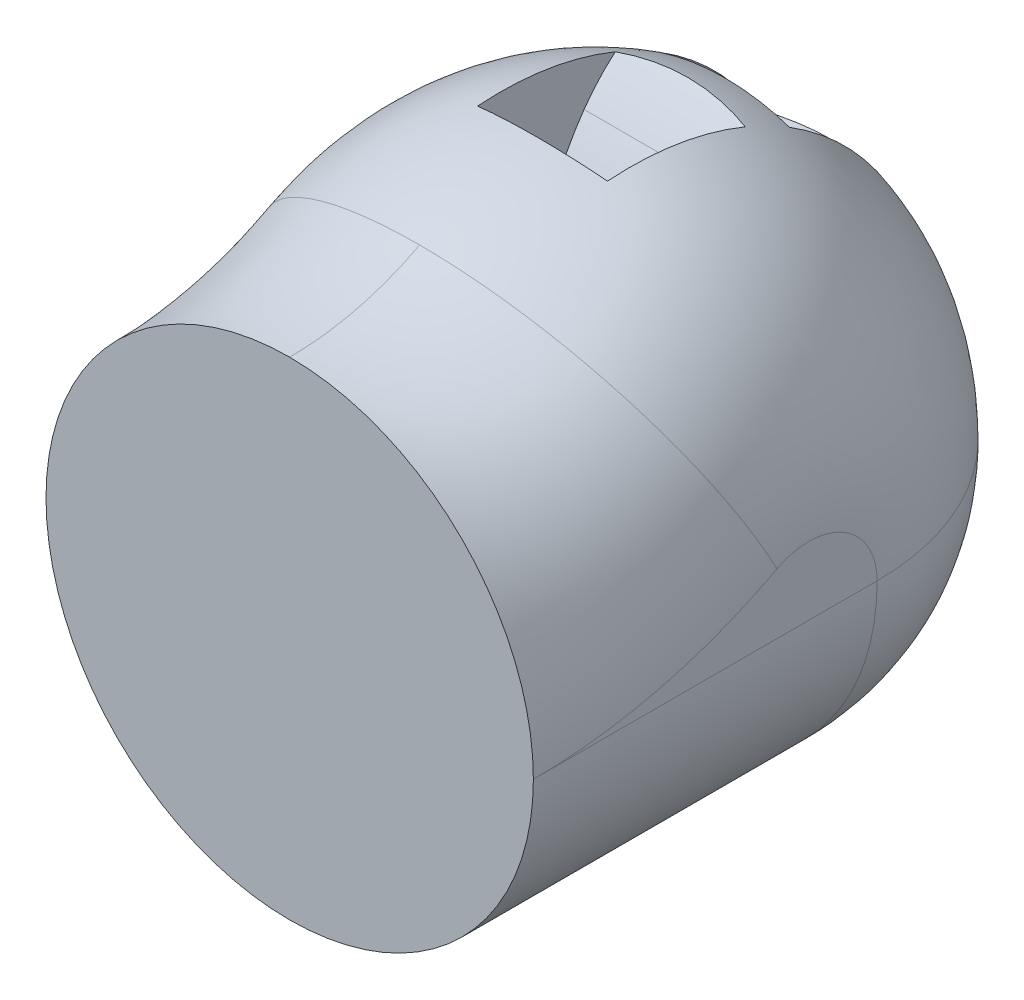
SolidWorks part; units mm, degrees
ref_plane "Front Plane" through (0, 0, 0) normal (0, 0, 1) x (1, 0, 0)
ref_plane "Top Plane" through (0, 0, 0) normal (0, 1, 0) x (1, 0, 0)
ref_plane "Right Plane" through (0, 0, 0) normal (1, 0, 0) x (0, 0, -1)
sketch "Sketch1" plane through (0, 0, 0) normal (1, 0, 0) x (0, 0, -1)
  line L1 (-21.2, 0) -> (-21.2, 18.75)
  line L4 (-21.2, 0) -> (24, 0)
  line L5 (-21.2, 18.75) -> (14.9812, 18.75) construction
  line L7 (-21.2, 0) -> (-21.2, -18.75)
  line L8 (-21.2, -18.75) -> (5.25, -18.75)
  arc A0 (-11.2, 21.2264) -> (24, 0) centre (0, 0) cw
  arc A1 (-21.2, 18.75) -> (-11.2, 21.2264) centre (-21.2, 40.1786) ccw
  arc A2 (24, 0) -> (5.25, -18.75) centre (5.25, 0) cw
  dimension "D2" = 24
  dimension "D1" = 18.75
  dimension "D3" = 10
extrude "Boss-Extrude1" add sketch "Sketch1" along normal blind 18.75 and the other way blind 18.75 contours L5 L1 L4 A0 | A1 L5 A0 | A2 L4 L7 L8 region at (0, 9.0604, -0.1104) region at (0, -8.8681, 0.3992) region at (0, 20.8273, 0.4304)
fillet "Fillet1" radius 18.75 8 edges at (18.75, -18.75, 7.975) (18.75, -13.2583, -18.5083) (18.75, 20.5524, -12.3936) (-18.75, -18.75, 7.975) (-18.75, -13.2583, -18.5083) (-18.75, 20.5524, -12.3936) (18.75, 19.3783, 16.0489) (-18.75, 19.3783, 16.0489)
sketch "Sketch2" plane through (0, 0, 0) normal (1, 0, 0) x (0, 0, -1)
  line L0 (0, 0) -> (0, 24) construction
  line L1 (0, 0) -> (6.449, 18.9317) construction
  line L2 (0, 0) -> (14.1068, 19.4164) construction
  line L3 (0, 0) -> (16.3452, 11.5254) construction
  line L4 (0, 0) -> (19.998, -0.2832) construction
  line L5 (0, 0) -> (16.0123, -11.9836) construction
  line L6 (0, 0) -> (6.449, 18.9317) construction
  line L7 (0, 0) -> (16.3452, 11.5254) construction
  line L8 (16.3452, 11.5254) -> (9.1072, 21.7902) construction
  line L9 (19.998, -0.2832) -> (20.3537, 24.8343) construction
  line L10 (16.0123, -11.9836) -> (38.5894, 18.1835) construction
  line L11 (10.8958, 21.3842) -> (0, 0) construction
  line L12 (0, 0) -> (9.2784, 11.7861) construction
  line L13 (0, 0) -> (14.4341, 4.0814) construction
  line L14 (0, 0) -> (9.2784, 11.7861) construction
  line L15 (0, 0) -> (0.5787, 14.9888) construction
  circle A0 centre (0, 0) radius 20 construction
  circle A1 centre (0, 0) radius 15 construction
  arc A2 (24, 0) -> (-11.2, 21.2264) centre (0, 0) ccw construction
  arc A3 (11.7557, 16.1803) -> (6.449, 18.9317) centre (0, 0) ccw construction
  arc A5 (6.449, 18.9317) -> (20.3537, 24.8343) centre (18.1365, 10.7285) cw construction
  arc A6 (6.449, 18.9317) -> (4.0814, 14.4341) centre (22.8165, 7.4437) ccw
  arc A7 (11.5254, 16.3452) -> (12.2935, 20.6124) centre (-1.9809, 20.9788) ccw
  arc A8 (6.449, 18.9317) -> (9.4499, 22.0613) centre (18.1365, 10.7285) cw
  arc A9 (9.4499, 22.0613) -> (12.2935, 20.6124) centre (0, 0) cw
  arc A10 (11.5254, 16.3452) -> (9.2784, 11.7861) centre (-7.3891, 22.8342) cw
  arc A11 (16.3452, 11.5254) -> (11.7861, 9.2784) centre (22.8342, -7.3891) ccw
  arc A12 (16.3452, 11.5254) -> (20.6124, 12.2935) centre (20.9788, -1.9809) cw
  arc A13 (20.6124, 12.2935) -> (22.0613, 9.4499) centre (0, 0) cw
  arc A14 (18.9317, 6.449) -> (22.0613, 9.4499) centre (10.7285, 18.1365) ccw
  arc A15 (18.9317, 6.449) -> (14.4341, 4.0814) centre (7.4437, 22.8165) cw
  arc A16 (19.998, -0.2832) -> (14.9888, 0.5787) centre (14.13, -19.3995) ccw
  arc A17 (19.998, -0.2832) -> (23.9017, -2.17) centre (15.8079, -13.9336) cw
  arc A18 (23.9017, -2.17) -> (23.4024, -5.3222) centre (0, 0) cw
  arc A19 (19.1067, -5.9104) -> (23.4024, -5.3222) centre (19.3399, 8.3667) ccw
  arc A20 (19.1067, -5.9104) -> (14.0764, -5.1822) centre (19.4333, 14.0836) cw
  arc A21 (16.0123, -11.9836) -> (12.4664, -8.342) centre (0.0287, -24) ccw
  arc A22 (16.0123, -11.9836) -> (18.0614, -15.8047) centre (4.5989, -20.5641) cw
  arc A23 (14.0764, -5.1822) -> (12.4664, -8.342) centre (0, 0) cw
  arc A24 (14.9888, 0.5787) -> (14.4341, 4.0814) centre (0, 0) ccw
  arc A25 (11.7861, 9.2784) -> (9.2784, 11.7861) centre (0, 0) ccw
  arc A26 (11.9836, -16.0123) -> (8.342, -12.4664) centre (24, -0.0287) cw [skipped]
  arc A27 (11.9836, -16.0123) -> (15.8047, -18.0614) centre (20.5641, -4.5989) ccw [skipped]
  arc A28 (18.0614, -15.8047) -> (15.8047, -18.0614) centre (0, 0) cw [skipped]
  arc A29 (-0.2832, 19.998) -> (0.5787, 14.9888) centre (-19.3995, 14.13) cw
  arc A30 (-0.2832, 19.998) -> (-2.17, 23.9017) centre (-13.9336, 15.8079) ccw
  arc A31 (0.5787, 14.9888) -> (4.0814, 14.4341) centre (0, 0) cw
  arc A32 (-2.17, 23.9017) -> (18.0614, -15.8047) centre (25.6062, 13.047) cw
  dimension "D1" = 40
  dimension "D2" = 30
  dimension "D4" = 6
  dimension "D5" = 4
  dimension "D7" = 12.56
  dimension "D3" = 36
  dimension "D6" = 36
  dimension "D8" = 25.12
  dimension "D9" = 37.68
  dimension "D10" = 9
  dimension "D12" = 36
  dimension "D14" = 36
  dimension "D11" = 4
  dimension "D13" = 2
extrude "Cut-Extrude1" cut sketch "Sketch2" against normal blind 5 and the other way blind 5 contours A32 A22 A21 A23 A20 A19 A18 A17 A16 A24 A15 A14 A13 A12 A11 A25 A10 A7 A9 A8 A6 A31 A29 A30
